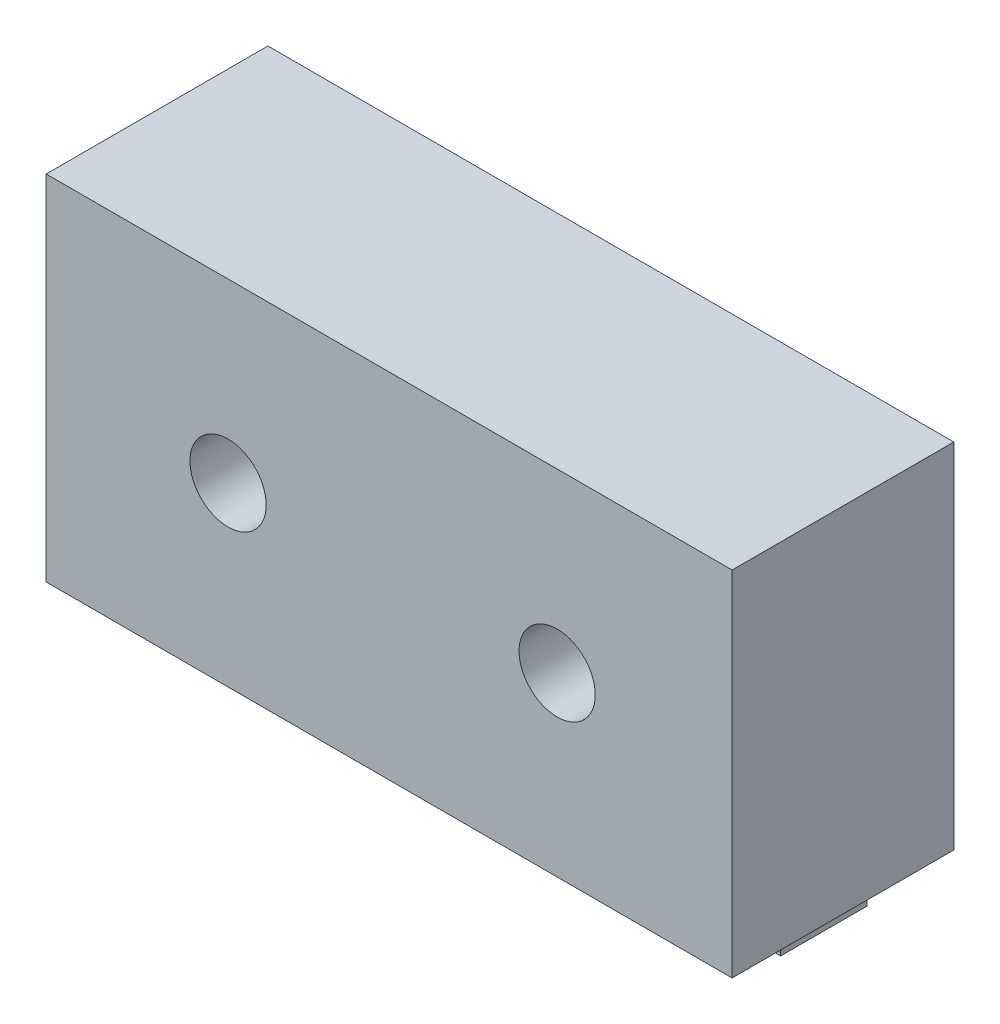
SolidWorks part; units mm, degrees
ref_plane "Front Plane" through (0, 0, 0) normal (0, 0, 1) x (1, 0, 0)
ref_plane "Top Plane" through (0, 0, 0) normal (0, 1, 0) x (1, 0, 0)
ref_plane "Right Plane" through (0, 0, 0) normal (1, 0, 0) x (0, 0, -1)
ref_plane "Switch Face" through (0, 0, 13.6) normal (0, 0, 1) x (1, 0, 0)
sketch "Case Sketch" plane through (0, 0, 13.6) normal (0, 0, 1) x (1, 0, 0)
  line L0 (-866, 150.5) -> (-846.2, 150.5)
  line L1 (-846.2, 150.5) -> (-846.2, 160.7)
  line L2 (-846.2, 160.7) -> (-866, 160.7)
  line L3 (-866, 160.7) -> (-866, 150.5)
extrude "Case" add sketch "Case Sketch" along normal blind 6.4
ref_axis "Engine Axis" through (-845.21, 0, 0) along (-1, 0, 0)
sketch "Screw Holes Sketch" plane through (0, 0, 0) normal (0, 0, 1) x (1, 0, 0)
  circle A0 centre (-860.75, 155.6) radius 1.1
  circle A1 centre (-851.25, 155.6) radius 1.1
extrude "Screw Holes" cut sketch "Screw Holes Sketch" against normal mid plane 60
ref_plane "Plunger Plane" through (0, 0, 15.55) normal (0, 0, 1) x (1, 0, 0)
sketch "Plunger Sketch" plane through (0, 0, 15.55) normal (0, 0, 1) x (1, 0, 0)
  line L0 (-849.25, 149.8) -> (-846.75, 149.8)
  line L1 (-846.75, 149.8) -> (-846.75, 150.5)
  line L2 (-846.75, 150.5) -> (-849.25, 150.5)
  line L3 (-849.25, 150.5) -> (-849.25, 149.8)
extrude "Plunger" add sketch "Plunger Sketch" along normal blind 2.5
